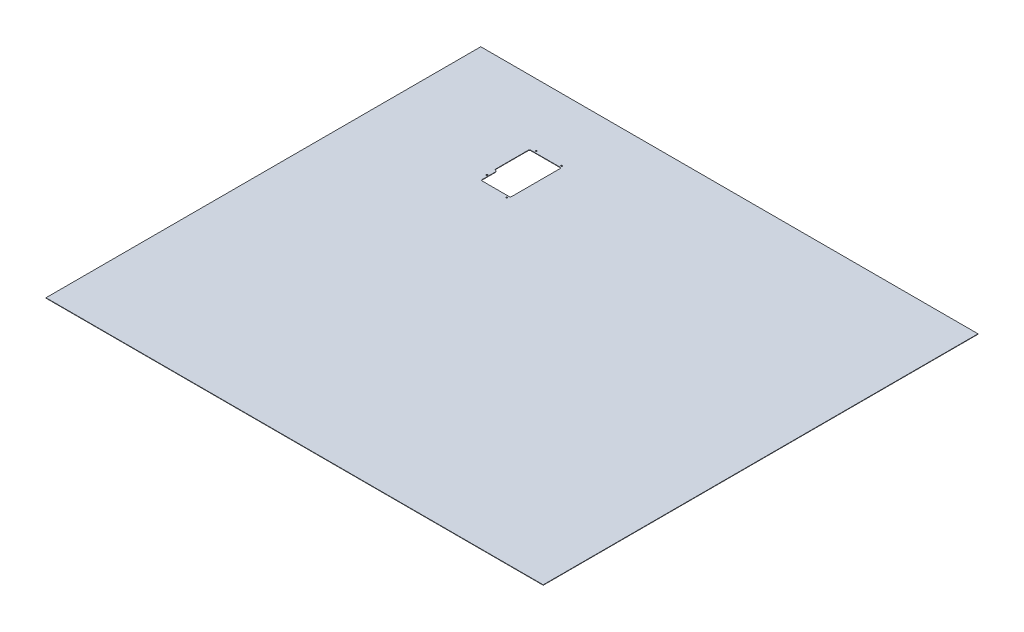
SolidWorks part; units mm, degrees
ref_plane "Front Plane" through (0, 0, 0) normal (0, 0, 1) x (1, 0, 0)
ref_plane "Top Plane" through (0, 0, 0) normal (0, 1, 0) x (1, 0, 0)
ref_plane "Right Plane" through (0, 0, 0) normal (1, 0, 0) x (0, 0, -1)
sketch "Sketch1" plane through (0, 0, 0) normal (0, 1, 0) x (1, 0, 0)
  line L1 (-625, 546.5) -> (625, 546.5)
  line L2 (-625, 546.5) -> (-625, -546.5)
  line L3 (-625, -546.5) -> (625, -546.5)
  line L4 (625, 546.5) -> (625, -546.5)
  line L5 (-625, 546.5) -> (625, -546.5) construction
  line L6 (-625, -546.5) -> (625, 546.5) construction
  point P0 (0, 0)
  dimension "D1" = 1250
  dimension "D2" = 1093
extrude "Boss-Extrude1" add sketch "Sketch1" along normal blind 1
sketch "Sketch2" plane through (0, 1, 0) normal (0, 1, 0) x (1, 0, 0)
  line L0 (625, 546.5) -> (-625, 546.5) construction
  line L1 (-260, 256) -> (-340, 256)
  line L2 (-260, 256) -> (-260, 384)
  line L3 (-260, 384) -> (-340, 384)
  line L4 (-340, 256) -> (-340, 384)
  line L5 (-625, 546.5) -> (-625, -546.5) construction
  line L7 (-340, 256) -> (-334, 256)
  line L8 (-340, 256) -> (-340, 296)
  line L9 (-340, 296) -> (-334, 296)
  line L10 (-334, 256) -> (-334, 296)
  dimension "D1" = 128
  dimension "D2" = 80
  dimension "D3" = 162.5
  dimension "D4" = 285
  dimension "D5" = 40
  dimension "D6" = 6
extrude "Cut-Extrude1" cut sketch "Sketch2" against normal blind 10 contours L10 L1 L2 L3 L4 L9 region at (-299.112, 1, -321.056)
fillet "Fillet2" radius 3 6 edges at (-260, 0.5, -256) (-334, 0.5, -256) (-334, 0.5, -296) (-340, 0.5, -296) (-340, 0.5, -384) (-260, 0.5, -384)
sketch "Sketch3" plane through (0, 1, 0) normal (0, 1, 0) x (1, 0, 0)
  line L0 (-263, 384) -> (-337, 384) construction
  line L1 (-334, 259) -> (-334, 293) construction
  line L2 (-263, 256) -> (-331, 256) construction
  line L3 (-340, 299) -> (-340, 381) construction
  line L4 (-260, 259) -> (-260, 381) construction
  circle A0 centre (-264, 389) radius 1.75
  circle A1 centre (-328, 389) radius 1.75
  circle A2 centre (-338, 275) radius 1.75
  circle A3 centre (-264, 251) radius 1.75
  dimension "D1" = 3.5
  dimension "D2" = 3.5
  dimension "D3" = 3.5
  dimension "D4" = 3.5
  dimension "D5" = 5
  dimension "D6" = 5
  dimension "D7" = 4
  dimension "D8" = 5
  dimension "D9" = 12
  dimension "D10" = 4
  dimension "D11" = 19
  dimension "D12" = 4
extrude "Cut-Extrude2" cut sketch "Sketch3" against normal blind 10
